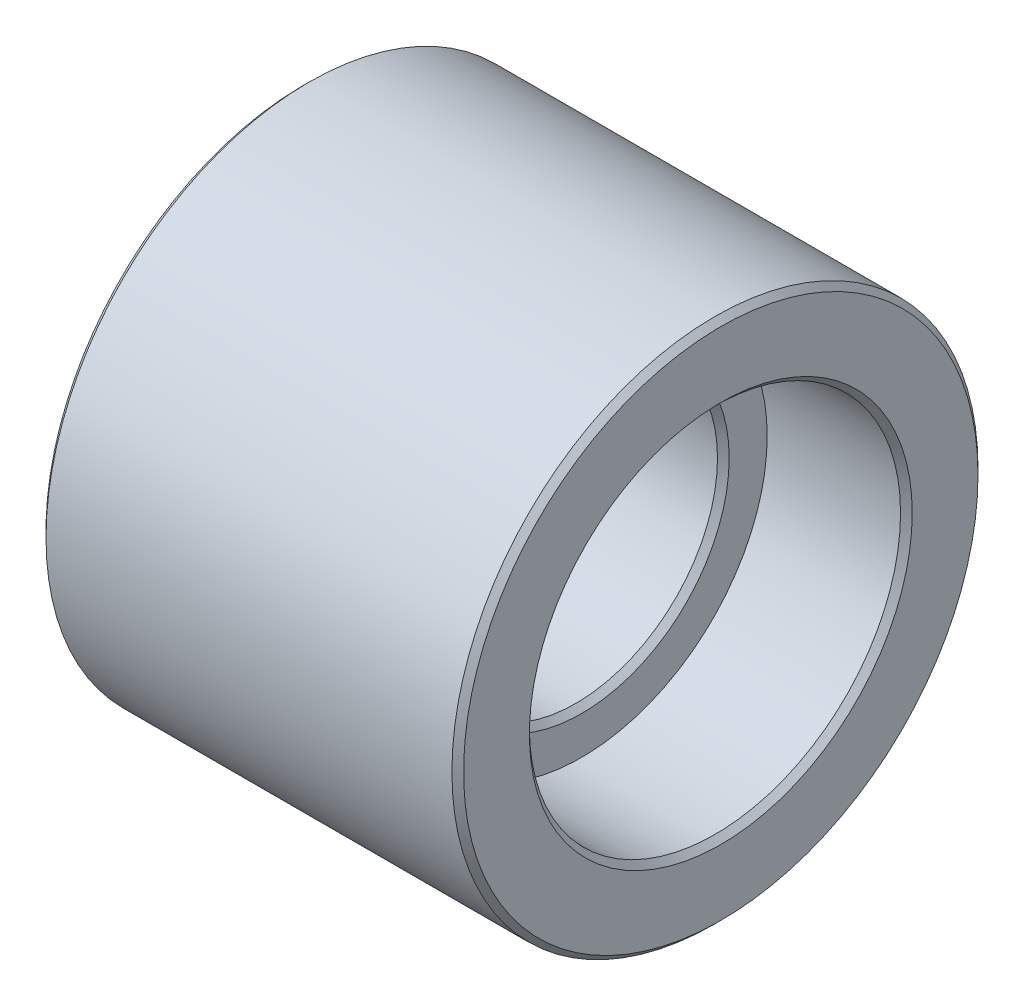
SolidWorks part; units mm, degrees
ref_plane "Front Plane" through (0, 0, 0) normal (0, 0, 1) x (1, 0, 0)
ref_plane "Top Plane" through (0, 0, 0) normal (0, 1, 0) x (1, 0, 0)
ref_plane "Right Plane" through (0, 0, 0) normal (1, 0, 0) x (0, 0, -1)
sketch "Sketch1" plane through (0, 0, 0) normal (0, 1, 0) x (1, 0, 0)
  line L0 (0, 9) -> (0, -9) construction
  line L1 (-7.1438, 9) -> (7.1438, 9)
  line L2 (7.1438, 9) -> (7.1438, 6.35)
  line L3 (7.1438, 6.35) -> (2.3813, 6.35)
  line L4 (2.3813, 6.35) -> (2.3813, 4.85)
  line L5 (2.3813, -6.35) -> (7.1438, -6.35)
  line L6 (7.1438, -6.35) -> (7.1438, -9)
  line L7 (7.1438, -9) -> (-7.1438, -9)
  line L8 (0, 0) -> (35.5203, 0) construction
  line L9 (2.3813, 4.85) -> (-2.3813, 4.85)
  line L10 (-7.1437, -6.35) -> (-7.1438, -9)
  line L11 (-2.3813, -4.85) -> (2.3813, -4.85)
  line L12 (2.3813, 4.85) -> (2.3813, 0) construction
  line L13 (2.3813, -4.85) -> (2.3813, -6.35)
  line L14 (2.3813, 0) -> (2.3813, -4.85) construction
  line L15 (-2.3813, -4.85) -> (-2.3812, -6.35)
  line L16 (-2.3812, -6.35) -> (-7.1437, -6.35)
  line L17 (-7.1438, 9) -> (-7.1437, 6.35)
  line L18 (-2.3812, 6.35) -> (-2.3813, 4.85)
  line L19 (-7.1437, 6.35) -> (-2.3812, 6.35)
  point P16 (0, 2.6544)
  point P17 (0, -2.6496)
  point P22 (0, -4.85)
  point P25 (0, 4.85)
  dimension "D1" = 4.7625
  dimension "D2" = 14.2875
  dimension "D3" = 1.5
  dimension "D4" = 12.7
  dimension "D5" = 18
revolve "Revolve1" add sketch "Sketch1" angle 360 about L8 region at (0, 0, -7.3456)
chamfer "Chamfer1" distance 0.2 angle 45 6 edges at (7.1438, 0, 9) (-7.1438, 0, 9) (-7.1437, 0, 6.35) (-2.3813, 0, 4.85) (2.3813, 0, 4.85) (7.1438, 0, 6.35)
